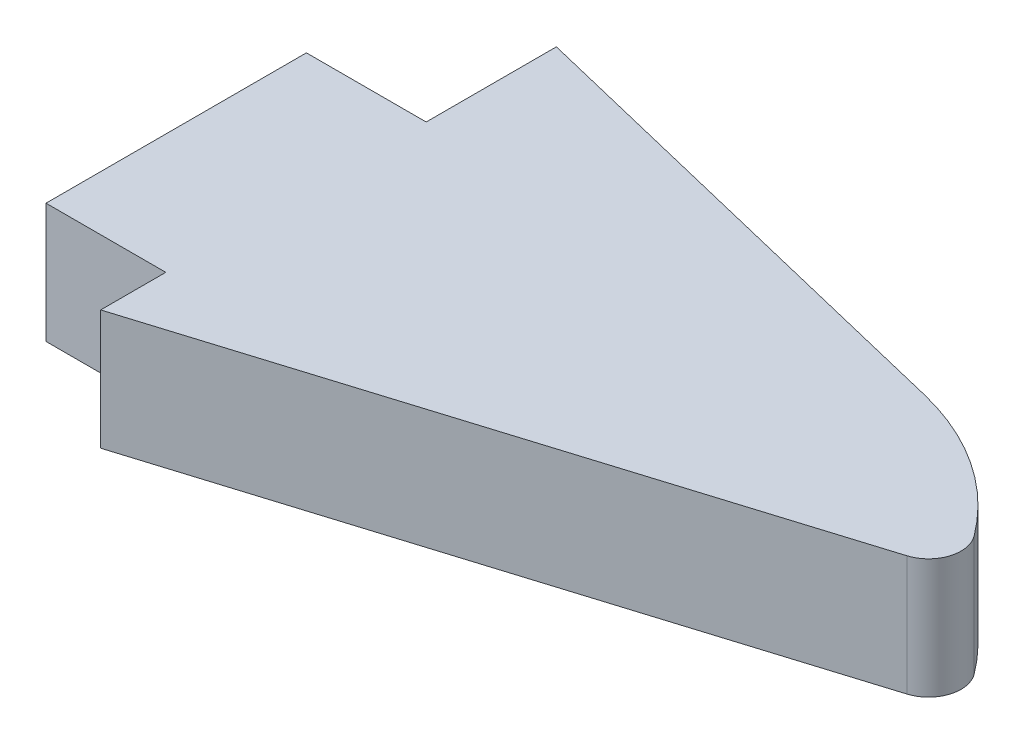
SolidWorks part; units mm, degrees
ref_plane "Front Plane" through (0, 0, 0) normal (0, 0, 1) x (1, 0, 0)
ref_plane "Top Plane" through (0, 0, 0) normal (0, 1, 0) x (1, 0, 0)
ref_plane "Right Plane" through (0, 0, 0) normal (1, 0, 0) x (0, 0, -1)
sketch "Sketch1" plane through (0, 0, 0) normal (0, 1, 0) x (1, 0, 0)
  line L0 (2.921, 6.35) -> (2.921, 12.7)
  line L1 (2.921, -6.35) -> (-2.921, -6.35)
  line L3 (2.921, 6.35) -> (-2.921, 6.35)
  line L4 (-2.921, -6.35) -> (-2.921, 6.35)
  line L5 (2.921, -6.35) -> (-2.921, 6.35) construction
  line L6 (2.921, 6.35) -> (-2.921, -6.35) construction
  line L7 (2.921, -6.35) -> (2.921, -9.525)
  line L8 (2.921, -9.525) -> (34.925, 0.3573)
  line L9 (34.925, 0.3573) -> (34.925, 4.9646)
  line L10 (34.925, 4.9646) -> (2.921, 12.7)
  line L11 (2.921, 12.7) -> (2.921, 6.35)
  point P0 (0, 0)
  dimension "D1" = 5.842
  dimension "D2" = 12.7
  dimension "D3" = 6.35
  dimension "D4" = 34.925
  dimension "D5" = 3.175
extrude "Boss-Extrude1" add sketch "Sketch1" along normal blind 5.842 contours L9 L10 L0 L3 L4 L1 L7 L8 region at (13.1487, 0, -1.7111)
fillet "Fillet1" radius 12.7 1 edges at (34.925, 2.921, -4.9646)
fillet "Fillet2" radius 1.5875 1 edges at (34.925, 2.921, -0.3573)
